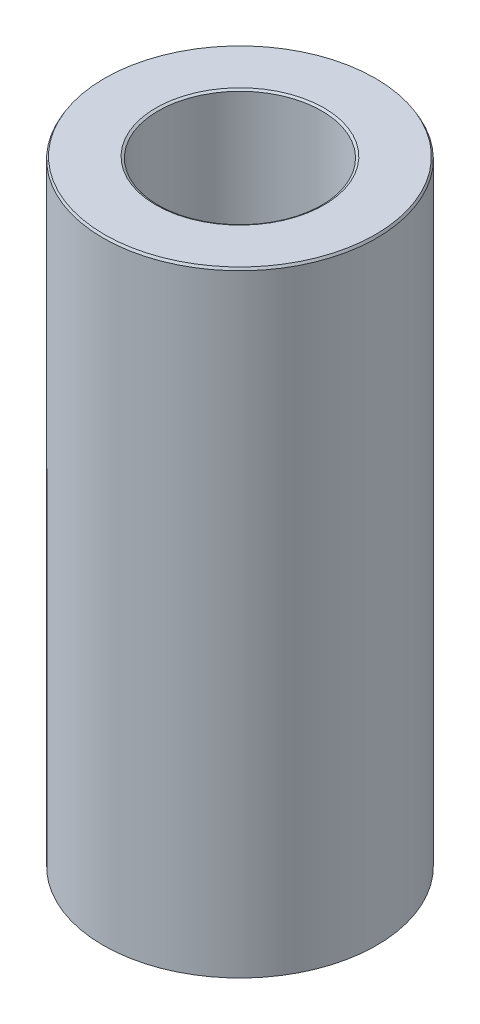
SolidWorks part; units mm, degrees
ref_plane "Front Plane" through (0, 0, 0) normal (0, 0, 1) x (1, 0, 0)
ref_plane "Top Plane" through (0, 0, 0) normal (0, 1, 0) x (1, 0, 0)
ref_plane "Right Plane" through (0, 0, 0) normal (1, 0, 0) x (0, 0, -1)
sketch "Sketch1" plane through (0, 0, 0) normal (0, 1, 0) x (1, 0, 0)
  circle A0 centre (0, 0) radius 57.5
  dimension "SLEEVE_OD" = 115
extrude "Boss-Extrude1" add sketch "Sketch1" along normal blind 259.087
sketch "Sketch2" plane through (0, 0, 0) normal (0, 1, 0) x (1, 0, 0)
  circle A0 centre (0, 0) radius 34.3759
  dimension "BORE_D" = 68.7518
extrude "Cut-Extrude1" cut sketch "Sketch2" along normal through all
chamfer "Chamfer1" distance 0.9825 angle 30 4 edges at (0, 259.087, 34.3759) (0, 0, 34.3759) (0, 0, 57.5) (0, 259.087, 57.5) first distance on face at (0, 259.087, 34.3759) first distance on face at (0, 0, 34.3759) first distance on face at (0, 259.087, 57.5)
